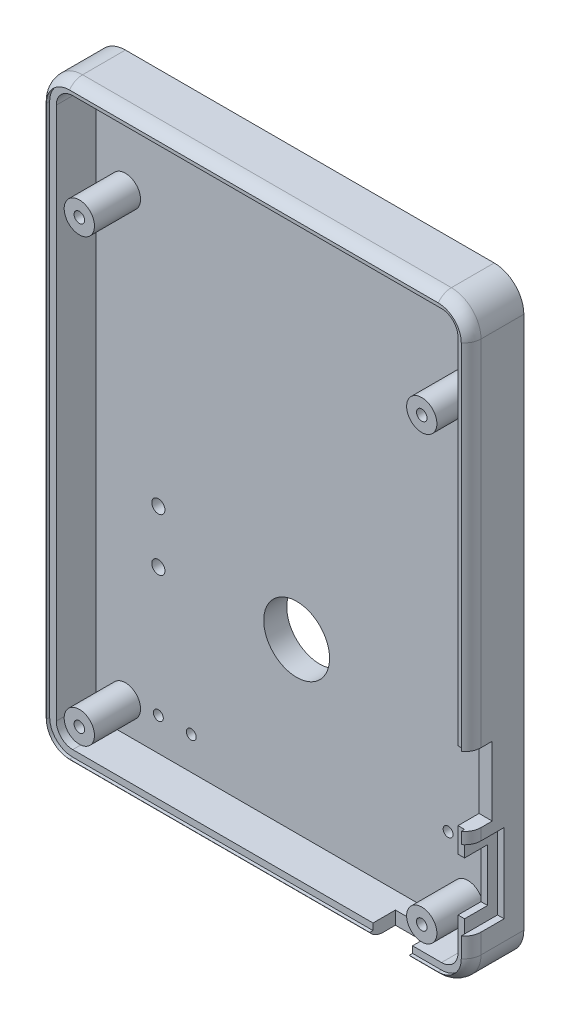
SolidWorks part; units mm, degrees
ref_plane "前基準面" through (0, 0, 0) normal (0, 0, 1) x (1, 0, 0)
ref_plane "上基準面" through (0, 0, 0) normal (0, 1, 0) x (1, 0, 0)
ref_plane "右基準面" through (0, 0, 0) normal (1, 0, 0) x (0, 0, -1)
sketch "草圖1" plane through (0, 0, 0) normal (0, 0, 1) x (1, 0, 0)
  line L0 (2, -2.5) -> (58, -2.5)
  line L1 (62.5, 2) -> (62.5, 83)
  line L2 (58, 87.5) -> (2, 87.5)
  line L3 (-2.5, 83) -> (-2.5, 2)
  arc A0 (58, -2.5) -> (62.5, 2) centre (58, 2) ccw
  arc A1 (62.5, 83) -> (58, 87.5) centre (58, 83) ccw
  arc A2 (2, 87.5) -> (-2.5, 83) centre (2, 83) ccw
  arc A3 (-2.5, 2) -> (2, -2.5) centre (2, 2) ccw
extrude "top plate" add sketch "草圖1" along normal blind 2
sketch "草圖2" plane through (0, 0, 0) normal (0, 0, 1) x (1, 0, 0)
  line L0 (2, -2.5) -> (58, -2.5)
  line L1 (62.5, 2) -> (62.5, 83)
  line L2 (58, 87.5) -> (2, 87.5)
  line L3 (-2.5, 83) -> (-2.5, 2)
  line L4 (2, -1.5) -> (58, -1.5)
  line L5 (61.5, 2) -> (61.5, 83)
  line L6 (58, 86.5) -> (2, 86.5)
  line L7 (-1.5, 83) -> (-1.5, 2)
  arc A0 (58, -2.5) -> (62.5, 2) centre (58, 2) ccw
  arc A1 (62.5, 83) -> (58, 87.5) centre (58, 83) ccw
  arc A2 (2, 87.5) -> (-2.5, 83) centre (2, 83) ccw
  arc A3 (-2.5, 2) -> (2, -2.5) centre (2, 2) ccw
  arc A4 (58, -1.5) -> (61.5, 2) centre (58, 2) ccw
  arc A5 (61.5, 83) -> (58, 86.5) centre (58, 83) ccw
  arc A6 (2, 86.5) -> (-1.5, 83) centre (2, 83) ccw
  arc A7 (-1.5, 2) -> (2, -1.5) centre (2, 2) ccw
extrude "wall outer half" add sketch "草圖2" along normal blind 9
sketch "草圖3" plane through (0, 0, 0) normal (0, 0, 1) x (1, 0, 0)
  line L0 (2, -1.5) -> (58, -1.5)
  line L1 (61.5, 2) -> (61.5, 83)
  line L2 (58, 86.5) -> (2, 86.5)
  line L3 (-1.5, 83) -> (-1.5, 2)
  line L4 (2, -0.5) -> (58, -0.5)
  line L5 (60.5, 2) -> (60.5, 83)
  line L6 (58, 85.5) -> (2, 85.5)
  line L7 (-0.5, 83) -> (-0.5, 2)
  arc A0 (58, -1.5) -> (61.5, 2) centre (58, 2) ccw
  arc A1 (61.5, 83) -> (58, 86.5) centre (58, 83) ccw
  arc A2 (2, 86.5) -> (-1.5, 83) centre (2, 83) ccw
  arc A3 (-1.5, 2) -> (2, -1.5) centre (2, 2) ccw
  arc A4 (58, -0.5) -> (60.5, 2) centre (58, 2) ccw
  arc A5 (60.5, 83) -> (58, 85.5) centre (58, 83) ccw
  arc A6 (2, 85.5) -> (-0.5, 83) centre (2, 83) ccw
  arc A7 (-0.5, 2) -> (2, -0.5) centre (2, 2) ccw
extrude "wall inner half" add sketch "草圖3" along normal blind 8
fillet "lens face round-over" radius 2.5 8 edges at (-1.182, -1.182, 9) (-2.5, 42.5, 9) (-1.182, 86.182, 9) (30, 87.5, 9) (61.182, 86.182, 9) (62.5, 42.5, 9) (61.182, -1.182, 9) (30, -2.5, 9)
sketch "草圖4" plane through (0, 0, 0) normal (0, 0, 1) x (1, 0, 0)
  circle A0 centre (30, 25) radius 8
  circle A1 centre (30, 25) radius 5
extrude "lens bezel ring" add sketch "草圖4" against normal blind 1.5
sketch "草圖5" plane through (0, 0, 0) normal (0, 0, 1) x (1, 0, 0)
  circle A0 centre (4, 4) radius 2.3
  circle A1 centre (56, 4) radius 2.3
  circle A2 centre (4, 71) radius 2.3
  circle A3 centre (56, 71) radius 2.3
extrude "corner posts" add sketch "草圖5" along normal blind 9
sketch "草圖6" plane through (0, 0, 0) normal (0, 0, 1) x (1, 0, 0)
  circle A0 centre (4, 4) radius 0.8
  circle A1 centre (56, 4) radius 0.8
  circle A2 centre (4, 71) radius 0.8
  circle A3 centre (56, 71) radius 0.8
extrude "post pilot holes M2" cut sketch "草圖6" against normal blind 6 from offset 9
sketch "草圖7" plane through (0, 0, 0) normal (0, 0, 1) x (1, 0, 0)
  line L0 (3.5, 49.5) -> (15.5, 49.5)
  line L1 (15.5, 49.5) -> (15.5, 50.5)
  line L2 (15.5, 50.5) -> (3.5, 50.5)
  line L3 (3.5, 50.5) -> (3.5, 49.5)
  line L4 (3.5, 53.5) -> (15.5, 53.5)
  line L5 (15.5, 53.5) -> (15.5, 54.5)
  line L6 (15.5, 54.5) -> (3.5, 54.5)
  line L7 (3.5, 54.5) -> (3.5, 53.5)
  line L8 (3.5, 57.5) -> (15.5, 57.5)
  line L9 (15.5, 57.5) -> (15.5, 58.5)
  line L10 (15.5, 58.5) -> (3.5, 58.5)
  line L11 (3.5, 58.5) -> (3.5, 57.5)
  line L12 (3.5, 61.5) -> (15.5, 61.5)
  line L13 (15.5, 61.5) -> (15.5, 62.5)
  line L14 (15.5, 62.5) -> (3.5, 62.5)
  line L15 (3.5, 62.5) -> (3.5, 61.5)
  line L16 (3.5, 65.5) -> (15.5, 65.5)
  line L17 (15.5, 65.5) -> (15.5, 66.5)
  line L18 (15.5, 66.5) -> (3.5, 66.5)
  line L19 (3.5, 66.5) -> (3.5, 65.5)
  line L20 (3.5, 69.5) -> (15.5, 69.5)
  line L21 (15.5, 69.5) -> (15.5, 70.5)
  line L22 (15.5, 70.5) -> (3.5, 70.5)
  line L23 (3.5, 70.5) -> (3.5, 69.5)
extrude "grip grooves" cut sketch "草圖7" along normal blind 0.6
sketch "草圖8" plane through (0, 0, 0) normal (0, 0, 1) x (1, 0, 0)
  circle A0 centre (9, 24) radius 1
  circle A1 centre (9, 32) radius 1
extrude "BOOT/RESET pinholes" cut sketch "草圖8" along normal through all
sketch "草圖9" plane through (0, 0, 0) normal (0, 1, 0) x (1, 0, 0)
  line L0 (47.6, -8.8) -> (53.6, -8.8)
  line L1 (53.6, -8.8) -> (53.6, -4.6)
  line L2 (53.6, -4.6) -> (47.6, -4.6)
  line L3 (47.6, -4.6) -> (47.6, -8.8)
extrude "shutter window" cut sketch "草圖9" against normal through all
sketch "草圖10" plane through (0, 0, 0) normal (0, 0, 1) x (1, 0, 0)
  circle A0 centre (30, 25) radius 5
extrude "lens hole" cut sketch "草圖10" along normal through all
sketch "草圖11" plane through (0, 0, 0) normal (0, 0, 1) x (1, 0, 0)
  circle A0 centre (14, 4.5) radius 0.75
  circle A1 centre (9, 4.5) radius 0.75
  circle A2 centre (53, 11.2) radius 0.75
extrude "LED light holes D1 D4 D5" cut sketch "草圖11" along normal through all
sketch "草圖12" plane through (0, 0, 0) normal (1, 0, 0) x (0, 0, -1)
  line L0 (-9, 18.75) -> (-4.8, 18.75)
  line L1 (-4.8, 18.75) -> (-4.8, 29.25)
  line L2 (-4.8, 29.25) -> (-9, 29.25)
  line L3 (-9, 29.25) -> (-9, 18.75)
extrude "USB-C window" cut sketch "草圖12" along normal blind 4.5 from offset 59
sketch "草圖13" plane through (0, 0, 0) normal (1, 0, 0) x (0, 0, -1)
  line L0 (-9, 7) -> (-4.5, 7)
  line L1 (-4.5, 7) -> (-4.5, 15)
  line L2 (-4.5, 15) -> (-9, 15)
  line L3 (-9, 15) -> (-9, 7)
extrude "power switch slot" cut sketch "草圖13" along normal blind 4.5 from offset 59
sketch "草圖14" plane through (0, 0, 0) normal (1, 0, 0) x (0, 0, -1)
  line L0 (-9, 5) -> (-3, 5)
  line L1 (-3, 5) -> (-3, 17)
  line L2 (-3, 17) -> (-9, 17)
  line L3 (-9, 17) -> (-9, 5)
extrude "switch finger pocket" cut sketch "草圖14" along normal blind 1.5 from offset 61.5
